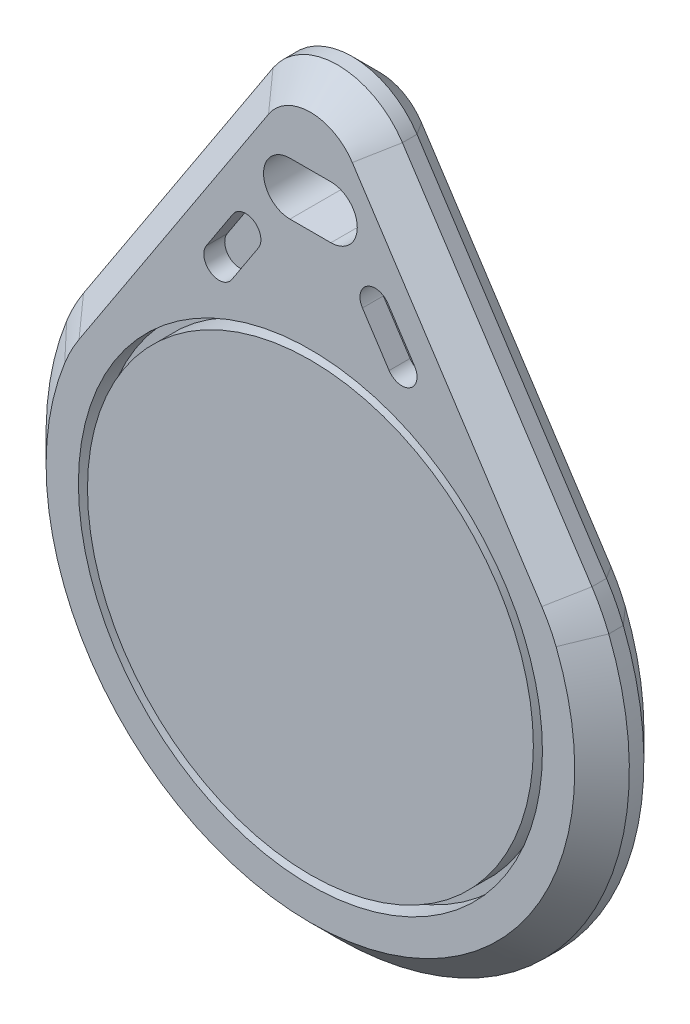
SolidWorks part; units mm, degrees
ref_plane "Plano frontal" through (0, 0, 0) normal (0, 0, 1) x (1, 0, 0)
ref_plane "Plano superior" through (0, 0, 0) normal (0, 1, 0) x (1, 0, 0)
ref_plane "Plano direito" through (0, 0, 0) normal (1, 0, 0) x (0, 0, -1)
sketch "Esboço1" plane through (0, 0, 0) normal (0, 0, 1) x (1, 0, 0)
  line L0 (0, 25.5447) -> (0, 0) construction
  line L1 (1.125, 21.2947) -> (-1.125, 21.2947) construction
  line L2 (-13.9695, 7.6957) -> (-3.5571, 23.6205)
  line L3 (0, 0) -> (0, -14.7053) construction
  line L4 (13.9695, 7.6957) -> (3.5571, 23.6205)
  line L5 (1.125, 19.8447) -> (-1.125, 19.8447) construction
  line L6 (1.125, 18.3947) -> (-1.125, 18.3947)
  line L7 (1.125, 21.2947) -> (-1.125, 21.2947)
  line L8 (-3.5571, 16.6127) -> (-5.0237, 14.3697) construction
  line L9 (-2.8583, 16.1558) -> (-4.3249, 13.9127)
  line L10 (-4.256, 17.0697) -> (-5.7226, 14.8266)
  line L11 (3.5571, 16.6127) -> (5.0237, 14.3697) construction
  line L12 (2.8583, 16.1558) -> (4.3249, 13.9127)
  line L13 (4.256, 17.0697) -> (5.7226, 14.8266)
  arc A0 (-14.8942, 5.9131) -> (14.8942, 5.9131) centre (0, 0) ccw
  arc A1 (3.5571, 23.6205) -> (-3.5571, 23.6205) centre (0, 21.2947) ccw
  arc A2 (-13.9695, 7.6957) -> (-14.8942, 5.9131) centre (-5.5998, 2.2232) ccw
  arc A3 (13.9695, 7.6957) -> (14.8942, 5.9131) centre (5.5998, 2.2232) cw
  arc A4 (1.125, 18.3947) -> (1.125, 21.2947) centre (1.125, 19.8447) ccw
  arc A5 (-1.125, 21.2947) -> (-1.125, 18.3947) centre (-1.125, 19.8447) ccw
  circle A6 centre (0, 0) radius 12.75
  circle A7 centre (0, 0) radius 12.25
  arc A8 (-2.8583, 16.1558) -> (-4.256, 17.0697) centre (-3.5571, 16.6127) ccw
  arc A9 (-5.7226, 14.8266) -> (-4.3249, 13.9127) centre (-5.0237, 14.3697) ccw
  arc A10 (2.8583, 16.1558) -> (4.256, 17.0697) centre (3.5571, 16.6127) cw
  arc A11 (5.7226, 14.8266) -> (4.3249, 13.9127) centre (5.0237, 14.3697) cw
  point P17 (0, 19.8447)
  point P27 (-4.2904, 15.4912)
  point P34 (4.2904, 15.4912)
  dimension "D1" = 32.05
  dimension "D4" = 4.25
  dimension "D2" = 10
  dimension "D3" = 1.45
  dimension "D7" = 25.5
  dimension "D6" = 5.15
  dimension "D10" = 4.35
  dimension "D5" = 40.25
  dimension "D9" = 1.67
  dimension "D11" = 3
  dimension "D8" = 0.5
extrude "Ressalto-extrusão1" add sketch "Esboço1" along normal mid plane 3.8 contours A3 L4 A1 L2 A2 A0 A5 L7 A4 L6 A6 A9 L10 A8 L9 L13 A11 L12 A10 | A7 region at (-8.324, 15.3708, 0) region at (0, 0, 0)
extrude "Ressalto-extrusão2" add sketch "Esboço1<3>" along normal mid plane 1.5 contours L10 A9 L9 A8 | A6 A7 | L12 A11 L13 A10 region at (-4.2904, 15.4912, 0) region at (-12.3894, 0, 0)
sketch "Esboço1<3>" plane through (0, 0, 0) normal (0, 0, 1) x (1, 0, 0) same geometry as "Esboço1"
chamfer "Chanfro1" distance 1.5 angle 45 12 edges at (-14.4767, 6.8276, -1.9) (0, -16.025, -1.9) (-8.7633, 15.6581, -1.9) (14.4767, 6.8276, -1.9) (0, 25.5447, -1.9) (8.7633, 15.6581, -1.9) (0, -16.025, 1.9) (14.4767, 6.8276, 1.9) (-14.4767, 6.8276, 1.9) (8.7633, 15.6581, 1.9) (-8.7633, 15.6581, 1.9) (0, 25.5447, 1.9)
extrude "Ressalto-extrusão3" add sketch "Esboço1<4>" against normal blind 1.9 contours A6 | A7
sketch "Esboço1<4>" plane through (0, 0, 0) normal (0, 0, 1) x (1, 0, 0) same geometry as "Esboço1"
